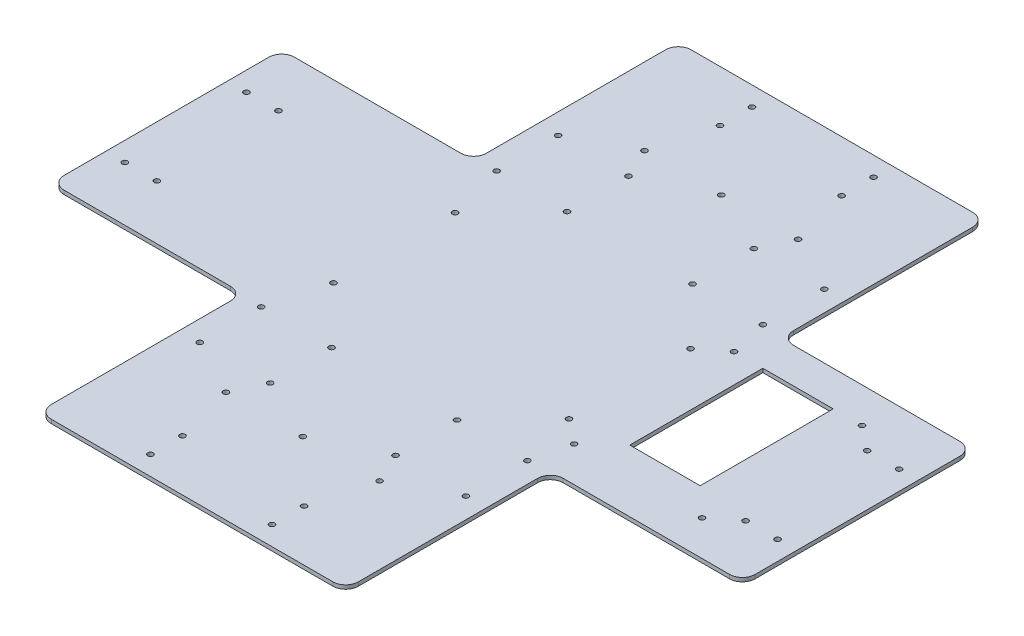
SolidWorks part; units mm, degrees
ref_plane "Front Plane" through (0, 0, 0) normal (0, 0, 1) x (1, 0, 0)
ref_plane "Top Plane" through (0, 0, 0) normal (0, 1, 0) x (1, 0, 0)
ref_plane "Right Plane" through (0, 0, 0) normal (1, 0, 0) x (0, 0, -1)
sketch "Sketch1" plane through (0, 0, 0) normal (0, 1, 0) x (1, 0, 0)
  line L0 (120, 250) -> (-120, 250)
  line L1 (-120, 250) -> (-120, 90)
  line L2 (-120, 90) -> (-270, 90)
  line L3 (-270, 90) -> (-270, -90)
  line L4 (0, 319.0603) -> (0, -214.0477) construction
  line L5 (-295.2994, 0) -> (181.6639, 0) construction
  line L6 (270, 90) -> (270, -90)
  line L7 (120, 90) -> (270, 90)
  line L8 (120, 250) -> (120, 90)
  line L9 (120, -250) -> (120, -90)
  line L10 (120, -90) -> (270, -90)
  line L11 (-120, -90) -> (-270, -90)
  line L12 (-120, -250) -> (-120, -90)
  line L13 (120, -250) -> (-120, -250)
  point P14 (0, 250)
  point P15 (-270, 0)
  point P16 (270, 0)
  point P20 (0, -250)
  dimension "D1" = 120
  dimension "D2" = 160
  dimension "150" = 150
  dimension "D3" = 90
extrude "Base" add sketch "Sketch1" along normal blind 3
fillet "Fillet1" radius 10 12 edges at (120, 1.5, -90) (270, 1.5, -90) (270, 1.5, 90) (120, 1.5, 90) (120, 1.5, 250) (-120, 1.5, 250) (-120, 1.5, 90) (-270, 1.5, 90) (-270, 1.5, -90) (-120, 1.5, -90) (-120, 1.5, -250) (120, 1.5, -250)
sketch "Sketch2" plane through (0, 3, 0) normal (0, 1, 0) x (1, 0, 0)
  line L0 (0, 268.1887) -> (0, -286.5172) construction
  line L1 (-278.1616, 0) -> (318.0529, 0) construction
  line L2 (110, 250) -> (-110, 250) construction
  line L3 (-270, 80) -> (-270, -80) construction
  circle A0 centre (-47.5, 235) radius 2.125
  circle A1 centre (-47.5, 210) radius 2.125
  circle A2 centre (-255, 47.5) radius 2.125
  circle A3 centre (-230, 47.5) radius 2.125
  circle A4 centre (-230, -47.5) radius 2.125
  circle A5 centre (-255, -47.5) radius 2.125
  circle A6 centre (255, -47.5) radius 2.125
  circle A7 centre (230, -47.5) radius 2.125
  circle A8 centre (230, 47.5) radius 2.125
  circle A9 centre (255, 47.5) radius 2.125
  circle A10 centre (47.5, 210) radius 2.125
  circle A11 centre (47.5, 235) radius 2.125
  circle A12 centre (47.5, -235) radius 2.125
  circle A13 centre (47.5, -210) radius 2.125
  circle A14 centre (-47.5, -210) radius 2.125
  circle A15 centre (-47.5, -235) radius 2.125
  dimension "D1" = 4.25
  dimension "D2" = 4.25
  dimension "D3" = 4.25
  dimension "D4" = 4.25
  dimension "D5" = 47.5
  dimension "D6" = 25
  dimension "D7" = 15
  dimension "D8" = 25
  dimension "D9" = 15
  dimension "D10" = 47.5
extrude "Armor Module Holes" cut sketch "Sketch2" against normal blind 3
sketch "Sketch3" plane through (0, 3, 0) normal (0, 1, 0) x (1, 0, 0)
  line L0 (-268.1887, 0) -> (424.969, 0) construction
  line L1 (0, 281.6655) -> (0, -321.0178) construction
  line L2 (-149.3232, 150) -> (229.1059, 150) construction
  line L3 (-149.3232, -150) -> (229.1059, -150) construction
  circle A0 centre (92, 47.5) radius 2.125
  circle A1 centre (92, -47.5) radius 2.125
  circle A2 centre (-92, -47.5) radius 2.125
  circle A3 centre (-92, 47.5) radius 2.125
  dimension "D2" = 4.25
  dimension "D1" = 150
  dimension "D3" = 47.5
  dimension "D4" = 92
extrude "Plates for Gimbal" cut sketch "Sketch3" against normal blind 3
sketch "Sketch5" plane through (0, 3, 0) normal (0, 1, 0) x (1, 0, 0)
  line L0 (0, 63.8605) -> (0, -71.0696) construction
  line L1 (-72.0204, 0) -> (84.8823, 0) construction
  line L2 (120, -240) -> (120, -100) construction
  line L3 (-110, -250) -> (110, -250) construction
  circle A0 centre (104, -92) radius 2.125
  circle A1 centre (104, -140) radius 2.125
  circle A2 centre (49, -92) radius 2.125
  circle A3 centre (49, -140) radius 2.125
  circle A4 centre (-49, -140) radius 2.125
  circle A5 centre (-49, -92) radius 2.125
  circle A6 centre (-104, -140) radius 2.125
  circle A7 centre (-104, -92) radius 2.125
  circle A8 centre (-104, 92) radius 2.125
  circle A9 centre (-104, 140) radius 2.125
  circle A10 centre (-49, 92) radius 2.125
  circle A11 centre (-49, 140) radius 2.125
  circle A12 centre (49, 140) radius 2.125
  circle A13 centre (49, 92) radius 2.125
  circle A14 centre (104, 140) radius 2.125
  circle A15 centre (104, 92) radius 2.125
  dimension "D1" = 4.25
  dimension "D2" = 4.25
  dimension "D5" = 4.25
  dimension "D6" = 4.25
  dimension "D3" = 48
  dimension "D4" = 16
  dimension "D7" = 55
  dimension "D8" = 110
extrude "Suspension Mount" cut sketch "Sketch5" against normal blind 10
sketch "Sketch6" plane through (0, 3, 0) normal (0, 1, 0) x (1, 0, 0)
  line L0 (-219.2229, 0) -> (231.3521, 0) construction
  line L1 (52.5596, 72.5) -> (282.564, 72.5) construction
  line L2 (52.5596, -72.5) -> (333.7759, -72.5) construction
  line L3 (92, 47.5) -> (230, 47.5) construction
  line L4 (161, 96.4976) -> (161, -82.3612) construction
  line L6 (133.5, 62.5) -> (188.5, 62.5)
  line L7 (133.5, 62.5) -> (133.5, -41.5)
  line L8 (133.5, -41.5) -> (188.5, -41.5)
  line L9 (188.5, 62.5) -> (188.5, -41.5)
  circle A2 centre (111, -62.5) radius 2.125
  circle A4 centre (211, -62.5) radius 2.125
  circle A5 centre (211, 62.5) radius 2.125
  circle A6 centre (111, 62.5) radius 2.125
  dimension "D3" = 10
  dimension "D4" = 50
  dimension "D6" = 4.25
  dimension "D1" = 72.5
  dimension "D2" = 72.5
  dimension "D9" = 69
  dimension "D12" = 55
  dimension "D13" = 27.5
  dimension "D14" = 10
  dimension "D15" = 104
extrude "Battery Mount" cut sketch "Sketch6" against normal blind 10
sketch "Sketch7" plane through (0, 3, 0) normal (0, 1, 0) x (1, 0, 0)
  line L0 (-120, -100) -> (-120, -240) construction
  line L1 (-78.7233, 0) -> (67.4924, 0) construction
  line L2 (-212.9337, -150) -> (270.4348, -150) construction
  line L3 (-212.9337, 150) -> (270.4348, 150) construction
  circle A0 centre (60, -163.5) radius 2.1
  circle A1 centre (0, -163.5) radius 2.125
  circle A2 centre (-60, -163.5) radius 2.125
  circle A3 centre (104, -140) radius 2.125 construction
  circle A4 centre (-60, 163.5) radius 2.125
  circle A5 centre (0, 163.5) radius 2.125
  circle A6 centre (60, 163.5) radius 2.1
  dimension "D2" = 4.2
  dimension "D3" = 4.25
  dimension "D4" = 4.25
  dimension "D1" = 23.5
  dimension "D5" = 60
  dimension "D6" = 60
  dimension "D7" = 60
  dimension "D8" = 150
extrude "Cut-Extrude1" cut sketch "Sketch7" against normal blind 10
